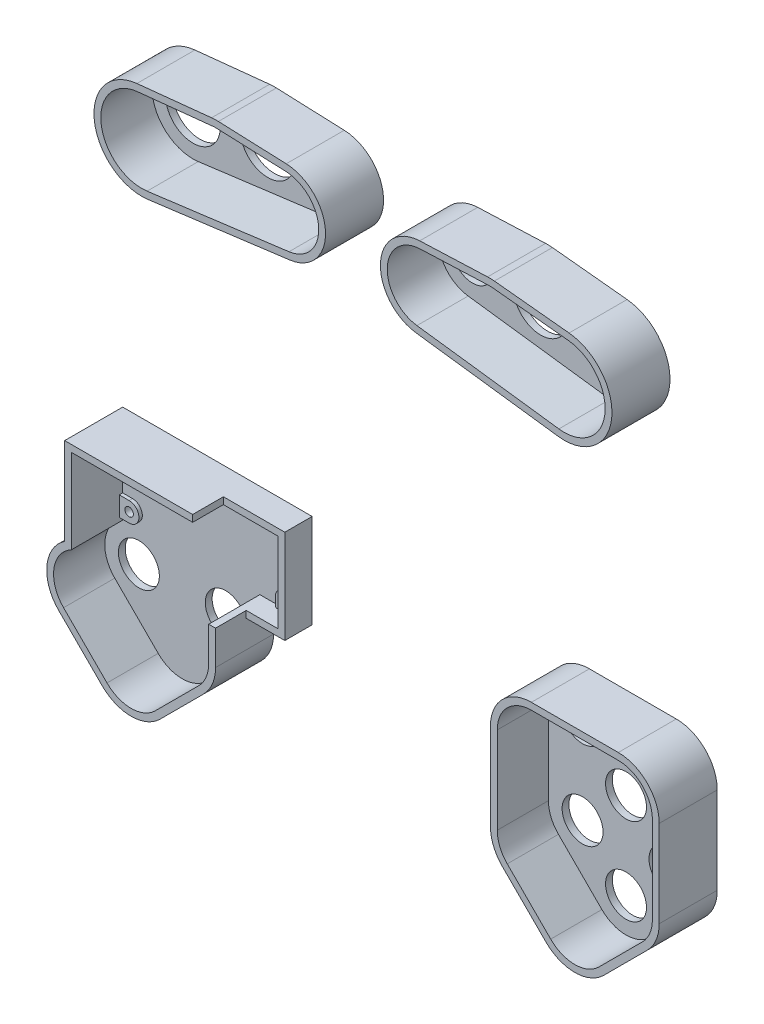
SolidWorks part; units mm, degrees
ref_plane "Front Plane" through (0, 0, 0) normal (0, 0, 1) x (1, 0, 0)
ref_plane "Top Plane" through (0, 0, 0) normal (0, 1, 0) x (1, 0, 0)
ref_plane "Right Plane" through (0, 0, 0) normal (1, 0, 0) x (0, 0, -1)
sketch "Sketch1" plane through (0, 0, 0) normal (0, 0, 1) x (1, 0, 0)
  line L10 (-86.2132, -68.4853) -> (-73.4853, -81.2132)
  line L11 (-56.5147, -81.2132) -> (-43.7868, -68.4853)
  line L12 (43.7868, -68.4853) -> (56.5147, -81.2132)
  line L13 (73.4853, -81.2132) -> (86.2132, -68.4853)
  line L14 (89.7279, -60) -> (89.7279, -34.5442)
  line L15 (63.3122, 76.6851) -> (41.4267, 78.9271)
  line L16 (39.439, 78.9888) -> (19.5552, 78.1913)
  line L17 (-19.5552, 78.1913) -> (-39.439, 78.9888)
  line L18 (-41.4267, 78.9271) -> (-63.3122, 76.6851)
  line L19 (-89.7279, -34.5442) -> (-89.7279, -60)
  line L20 (-86.2132, -68.4853) -> (-73.4853, -81.2132)
  line L21 (-56.5147, -81.2132) -> (-43.7868, -68.4853)
  line L22 (43.7868, -68.4853) -> (56.5147, -81.2132)
  line L23 (73.4853, -81.2132) -> (86.2132, -68.4853)
  line L24 (89.7279, -60) -> (89.7279, -34.5442)
  line L25 (63.3122, 76.6851) -> (41.4267, 78.9271)
  line L26 (39.439, 78.9888) -> (19.5552, 78.1913)
  line L27 (-19.5552, 78.1913) -> (-39.439, 78.9888)
  line L28 (-41.4267, 78.9271) -> (-63.3122, 76.6851)
  line L29 (-89.7279, -34.5442) -> (-89.7279, -60)
  line L30 (77.7279, -22.5442) -> (52.2721, -22.5442)
  line L31 (40.2721, -34.5442) -> (40.2721, -60)
  line L32 (-60.0743, 48.8756) -> (-18.4837, 54.3018)
  line L33 (60.0743, 48.8756) -> (18.4837, 54.3018)
  line L34 (-77.7279, -48) -> (-52.2721, -48)
  line L35 (-65, -48) -> (-65, -50) construction
  line L36 (-79.579, -29.36) -> (-33.859, -29.36)
  line L37 (-79.579, -29.36) -> (-79.579, -47.14)
  line L38 (-79.579, -47.14) -> (-33.859, -47.14)
  line L39 (-33.859, -29.36) -> (-33.859, -47.14)
  line L40 (-79.579, -29.36) -> (-33.859, -47.14) construction
  line L41 (-79.579, -47.14) -> (-33.859, -29.36) construction
  line L42 (-82.469, -26.5) -> (-30.969, -26.5)
  line L43 (-82.469, -26.5) -> (-82.469, -50)
  line L44 (-82.469, -50) -> (-30.969, -50)
  line L45 (-30.969, -26.5) -> (-30.969, -50)
  line L46 (-82.469, -26.5) -> (-30.969, -50) construction
  line L47 (-82.469, -50) -> (-30.969, -26.5) construction
  line L48 (-84.469, -52) -> (-28.969, -52)
  line L49 (-84.469, -52) -> (-84.469, -24.5)
  line L50 (-84.469, -24.5) -> (-28.969, -24.5)
  line L51 (-28.969, -52) -> (-28.969, -24.5)
  line L52 (-84.469, -52) -> (-28.969, -24.5) construction
  line L53 (-84.469, -24.5) -> (-28.969, -52) construction
  line L54 (-30.969, -26.5) -> (-28.969, -26.5) construction
  line L55 (-30.969, -26.5) -> (-30.969, -24.5) construction
  line L56 (-40.2721, -60) -> (-40.2721, -52)
  arc A16 (-89.7279, -60) -> (-86.2132, -68.4853) centre (-77.7279, -60) ccw
  arc A17 (-73.4853, -81.2132) -> (-56.5147, -81.2132) centre (-65, -72.7279) ccw
  arc A18 (43.7868, -68.4853) -> (-43.7868, -68.4853) centre (0, -112.2721) ccw
  arc A19 (56.5147, -81.2132) -> (73.4853, -81.2132) centre (65, -72.7279) ccw
  arc A20 (86.2132, -68.4853) -> (89.7279, -60) centre (77.7279, -60) ccw
  arc A21 (89.7279, -34.5442) -> (85.5204, -25.4185) centre (77.7279, -34.5442) ccw
  arc A22 (73.6585, 55.182) -> (85.5204, -25.4185) centre (125.7323, 21.6725) ccw
  arc A23 (73.6585, 55.182) -> (63.3122, 76.6851) centre (61.8855, 62.758) ccw
  arc A24 (41.4267, 78.9271) -> (39.439, 78.9888) centre (40, 65) ccw
  arc A25 (19.5552, 78.1913) -> (16.7836, 77.7518) centre (20.0361, 66.201) ccw
  arc A26 (-16.7836, 77.7518) -> (16.7836, 77.7518) centre (0, 137.3578) ccw
  arc A27 (-16.7836, 77.7518) -> (-19.5552, 78.1913) centre (-20.0361, 66.201) ccw
  arc A28 (-39.439, 78.9888) -> (-41.4267, 78.9271) centre (-40, 65) ccw
  arc A29 (-63.3122, 76.6851) -> (-73.6585, 55.182) centre (-61.8855, 62.758) ccw
  arc A30 (-85.5204, -25.4185) -> (-73.6585, 55.182) centre (-125.7323, 21.6725) ccw
  arc A31 (-85.5204, -25.4185) -> (-89.7279, -34.5442) centre (-77.7279, -34.5442) ccw
  arc A32 (-89.7279, -60) -> (-86.2132, -68.4853) centre (-77.7279, -60) ccw
  arc A33 (-73.4853, -81.2132) -> (-56.5147, -81.2132) centre (-65, -72.7279) ccw
  arc A34 (43.7868, -68.4853) -> (-43.7868, -68.4853) centre (0, -112.2721) ccw
  arc A35 (56.5147, -81.2132) -> (73.4853, -81.2132) centre (65, -72.7279) ccw
  arc A36 (86.2132, -68.4853) -> (89.7279, -60) centre (77.7279, -60) ccw
  arc A37 (89.7279, -34.5442) -> (85.5204, -25.4185) centre (77.7279, -34.5442) ccw
  arc A38 (73.6585, 55.182) -> (85.5204, -25.4185) centre (125.7323, 21.6725) ccw
  arc A39 (73.6585, 55.182) -> (63.3122, 76.6851) centre (61.8855, 62.758) ccw
  arc A40 (41.4267, 78.9271) -> (39.439, 78.9888) centre (40, 65) ccw
  arc A41 (19.5552, 78.1913) -> (16.7836, 77.7518) centre (20.0361, 66.201) ccw
  arc A42 (-16.7836, 77.7518) -> (16.7836, 77.7518) centre (0, 137.3578) ccw
  arc A43 (-16.7836, 77.7518) -> (-19.5552, 78.1913) centre (-20.0361, 66.201) ccw
  arc A44 (-39.439, 78.9888) -> (-41.4267, 78.9271) centre (-40, 65) ccw
  arc A45 (-63.3122, 76.6851) -> (-73.6585, 55.182) centre (-61.8855, 62.758) ccw
  arc A46 (-85.5204, -25.4185) -> (-73.6585, 55.182) centre (-125.7323, 21.6725) ccw
  arc A47 (-85.5204, -25.4185) -> (-89.7279, -34.5442) centre (-77.7279, -34.5442) ccw
  circle A48 centre (77.7279, -34.5442) radius 6 construction
  circle A49 centre (52.2721, -34.5442) radius 6 construction
  circle A50 centre (65, -47.2721) radius 6 construction
  circle A51 centre (77.7279, -60) radius 6 construction
  circle A52 centre (52.2721, -60) radius 6 construction
  circle A53 centre (65, -72.7279) radius 6 construction
  circle A54 centre (-52.2721, -60) radius 6 construction
  circle A55 centre (-77.7279, -60) radius 6 construction
  circle A56 centre (77.7279, -34.5442) radius 6
  circle A57 centre (52.2721, -34.5442) radius 6
  circle A58 centre (65, -47.2721) radius 6
  circle A59 centre (77.7279, -60) radius 6
  circle A60 centre (52.2721, -60) radius 6
  circle A61 centre (65, -72.7279) radius 6
  circle A62 centre (-52.2721, -60) radius 6
  circle A63 centre (-77.7279, -60) radius 6
  circle A64 centre (61.8855, 62.758) radius 8 construction
  circle A65 centre (40, 65) radius 8 construction
  circle A66 centre (20.0361, 66.201) radius 6 construction
  circle A67 centre (-20.0361, 66.201) radius 6 construction
  circle A68 centre (-40, 65) radius 8 construction
  circle A69 centre (-61.8855, 62.758) radius 8 construction
  circle A70 centre (61.8855, 62.758) radius 8
  circle A71 centre (40, 65) radius 8
  circle A72 centre (20.0361, 66.201) radius 6
  circle A73 centre (-20.0361, 66.201) radius 6
  circle A74 centre (-40, 65) radius 8
  circle A75 centre (-61.8855, 62.758) radius 8
  circle A76 centre (77.7279, -34.5442) radius 12
  circle A77 centre (52.2721, -34.5442) radius 12
  circle A78 centre (52.2721, -60) radius 12
  circle A79 centre (-61.8855, 62.758) radius 14
  circle A80 centre (-20.0361, 66.201) radius 12
  circle A81 centre (20.0361, 66.201) radius 12
  circle A82 centre (61.8855, 62.758) radius 14
  circle A83 centre (-77.7279, -60) radius 12
  circle A84 centre (-52.2721, -60) radius 12
  circle A85 centre (-79.579, -29.36) radius 1.25
  circle A86 centre (-33.859, -29.36) radius 1.25
  circle A87 centre (-33.859, -47.14) radius 1.25
  circle A88 centre (-79.579, -47.14) radius 1.25
  point P47 (-56.719, -38.25)
  point P66 (-56.719, -38.25)
  point P72 (-56.719, -38.25)
  dimension "D4" = 2.5
  dimension "D2" = 45.72
  dimension "D3" = 17.78
  dimension "D5" = 51.5
  dimension "D6" = 23.5
  dimension "D7" = 2
  dimension "D1" = 0
extrude "Boss-Extrude1" add sketch "Sketch1" along normal blind 2 contours A84 L34 A83 L20 A33 L21 | A83 A32 A63 | A84 A62 | A37 A76 A56 | A77 A58 A76 L30 | A77 A57 | A78 A58 A77 L31 | A78 L22 A35 L23 A36 L24 A76 A58 A61 A59 | A78 A60 | A79 A45 A75 | A80 A74 A79 L32 | A80 L27 A44 L28 A79 A74 | A43 A80 A73 | A41 A81 A72 | A82 L25 A40 L26 A81 A71 | A82 A71 A81 L33 | A39 A82 A70 | A84 L56 L48 | A84 L48 L51 L50 L49 A83 L43 L42 L45 L44 | L48 A84 L44 | A84 L44 A83 L48 | L48 A83 L44 L43 L49 | A88 A83 L43 L44 | A84 L34 A83 L44 | L44 A84 | A88 L37 A85 L36 A86 L39 A87 L38 A83 L34 A84 L44 L45 L42 L43 | A88 L38 A87 L39 A86 L36 A85 L37 region at (-65, -73.7209, 0) region at (-88.5141, -64.4678, 0) region at (-77.3432, -50.979, 0) region at (-83.8496, -37.2862, 0) region at (-65, -50.921, 0) region at (-60.3032, -68.4912, 0) region at (-77.3671, -49.1806, 0) region at (-81.9029, -37.7381, 0) region at (-52.2721, -51.0485, 0) region at (-65, -48.8938, 0) region at (52.2721, -72.6804, 0) region at (41.4991, -64.4623, 0) region at (-41.1646, -53.9455, 0) region at (-74.1443, 68.6564, 0) region at (-52.2721, -49.194, 0) region at (46.3766, -47.2721, 0) region at (-41.0869, 74.8949, 0) region at (-39.4755, 55.0305, 0) region at (-56.719, -38.25, 0) region at (44.0268, -26.2989, 0) region at (-27.4629, 57.2114, 0) region at (65, -28.6487, 0) region at (81.7633, -23.6041, 0) region at (18.2097, 77.7176, 0) region at (67.6138, 50.4188, 0) region at (41.0869, 74.8949, 0) region at (39.4755, 55.0305, 0)
sketch "Sketch2" plane through (0, 0, 2) normal (0, 0, 1) x (1, 0, 0)
  line L0 (40.2721, -34.5442) -> (40.2721, -60) construction
  line L1 (43.7868, -68.4853) -> (56.5147, -81.2132) construction
  line L2 (73.4853, -81.2132) -> (86.2132, -68.4853) construction
  line L3 (89.7279, -60) -> (89.7279, -34.5442) construction
  line L4 (77.7279, -22.5442) -> (52.2721, -22.5442) construction
  line L5 (18.4837, 54.3018) -> (60.0743, 48.8756) construction
  line L6 (63.3122, 76.6851) -> (41.4267, 78.9271) construction
  line L7 (39.439, 78.9888) -> (19.5552, 78.1913) construction
  line L8 (-19.5552, 78.1913) -> (-39.439, 78.9888) construction
  line L9 (-41.4267, 78.9271) -> (-63.3122, 76.6851) construction
  line L10 (-60.0743, 48.8756) -> (-18.4837, 54.3018) construction
  line L14 (40.2721, -34.5442) -> (40.2721, -60)
  line L15 (43.7868, -68.4853) -> (56.5147, -81.2132)
  line L16 (73.4853, -81.2132) -> (86.2132, -68.4853)
  line L17 (89.7279, -60) -> (89.7279, -34.5442)
  line L18 (77.7279, -22.5442) -> (52.2721, -22.5442)
  line L19 (18.4837, 54.3018) -> (60.0743, 48.8756)
  line L20 (63.3122, 76.6851) -> (41.4267, 78.9271)
  line L21 (39.439, 78.9888) -> (19.5552, 78.1913)
  line L22 (-19.5552, 78.1913) -> (-39.439, 78.9888)
  line L23 (-41.4267, 78.9271) -> (-63.3122, 76.6851)
  line L24 (-60.0743, 48.8756) -> (-18.4837, 54.3018)
  line L31 (-19.6354, 76.1929) -> (-39.5191, 76.9904)
  line L32 (-41.2229, 76.9375) -> (-63.1084, 74.6955)
  line L33 (-60.333, 50.8588) -> (-18.7424, 56.285)
  line L34 (18.7424, 56.285) -> (60.333, 50.8588)
  line L35 (63.1084, 74.6955) -> (41.2229, 76.9375)
  line L36 (39.5191, 76.9904) -> (19.6354, 76.1929)
  line L37 (42.2721, -34.5442) -> (42.2721, -60)
  line L38 (45.201, -67.0711) -> (57.9289, -79.799)
  line L39 (72.0711, -79.799) -> (84.799, -67.0711)
  line L40 (87.7279, -60) -> (87.7279, -34.5442)
  line L41 (77.7279, -24.5442) -> (52.2721, -24.5442)
  line L49 (-40.2721, -60) -> (-40.2721, -52)
  line L50 (-40.2721, -52) -> (-28.969, -52)
  line L51 (-28.969, -52) -> (-28.969, -24.5)
  line L52 (-28.969, -24.5) -> (-84.469, -24.5)
  line L53 (-84.469, -24.5) -> (-84.469, -50.0724)
  line L54 (-86.2132, -68.4853) -> (-73.4853, -81.2132)
  line L55 (-56.5147, -81.2132) -> (-43.7868, -68.4853)
  line L56 (-40.2721, -60) -> (-40.2721, -52)
  line L57 (-40.2721, -52) -> (-28.969, -52)
  line L58 (-28.969, -52) -> (-28.969, -24.5)
  line L59 (-28.969, -24.5) -> (-84.469, -24.5)
  line L60 (-84.469, -24.5) -> (-84.469, -50.0724)
  line L61 (-86.2132, -68.4853) -> (-73.4853, -81.2132)
  line L62 (-56.5147, -81.2132) -> (-43.7868, -68.4853)
  line L70 (-42.2721, -60) -> (-42.2721, -50)
  line L71 (-42.2721, -50) -> (-30.969, -50)
  line L72 (-30.969, -50) -> (-30.969, -26.5)
  line L73 (-30.969, -26.5) -> (-82.469, -26.5)
  line L74 (-82.469, -26.5) -> (-82.469, -51.1953)
  line L75 (-84.799, -67.0711) -> (-72.0711, -79.799)
  line L76 (-57.9289, -79.799) -> (-45.201, -67.0711)
  line L77 (-42.2721, -60) -> (-42.2721, -50)
  line L78 (-42.2721, -50) -> (-30.969, -50)
  line L79 (-30.969, -50) -> (-30.969, -26.5)
  line L80 (-30.969, -26.5) -> (-82.469, -26.5)
  line L81 (-82.469, -26.5) -> (-82.469, -51.1953)
  line L82 (-84.799, -67.0711) -> (-72.0711, -79.799)
  line L83 (-57.9289, -79.799) -> (-45.201, -67.0711)
  arc A0 (40.2721, -60) -> (43.7868, -68.4853) centre (52.2721, -60) ccw construction
  arc A1 (56.5147, -81.2132) -> (73.4853, -81.2132) centre (65, -72.7279) ccw construction
  arc A2 (86.2132, -68.4853) -> (89.7279, -60) centre (77.7279, -60) ccw construction
  arc A3 (89.7279, -34.5442) -> (77.7279, -22.5442) centre (77.7279, -34.5442) ccw construction
  arc A4 (52.2721, -22.5442) -> (40.2721, -34.5442) centre (52.2721, -34.5442) ccw construction
  arc A5 (60.0743, 48.8756) -> (63.3122, 76.6851) centre (61.8855, 62.758) ccw construction
  arc A6 (41.4267, 78.9271) -> (39.439, 78.9888) centre (40, 65) ccw construction
  arc A7 (19.5552, 78.1913) -> (18.4837, 54.3018) centre (20.0361, 66.201) ccw construction
  arc A8 (-18.4837, 54.3018) -> (-19.5552, 78.1913) centre (-20.0361, 66.201) ccw construction
  arc A9 (-39.439, 78.9888) -> (-41.4267, 78.9271) centre (-40, 65) ccw construction
  arc A10 (-63.3122, 76.6851) -> (-60.0743, 48.8756) centre (-61.8855, 62.758) ccw construction
  arc A14 (40.2721, -60) -> (43.7868, -68.4853) centre (52.2721, -60) ccw
  arc A15 (56.5147, -81.2132) -> (73.4853, -81.2132) centre (65, -72.7279) ccw
  arc A16 (86.2132, -68.4853) -> (89.7279, -60) centre (77.7279, -60) ccw
  arc A17 (89.7279, -34.5442) -> (77.7279, -22.5442) centre (77.7279, -34.5442) ccw
  arc A18 (52.2721, -22.5442) -> (40.2721, -34.5442) centre (52.2721, -34.5442) ccw
  arc A19 (60.0743, 48.8756) -> (63.3122, 76.6851) centre (61.8855, 62.758) ccw
  arc A20 (41.4267, 78.9271) -> (39.439, 78.9888) centre (40, 65) ccw
  arc A21 (19.5552, 78.1913) -> (18.4837, 54.3018) centre (20.0361, 66.201) ccw
  arc A22 (-18.4837, 54.3018) -> (-19.5552, 78.1913) centre (-20.0361, 66.201) ccw
  arc A23 (-39.439, 78.9888) -> (-41.4267, 78.9271) centre (-40, 65) ccw
  arc A24 (-63.3122, 76.6851) -> (-60.0743, 48.8756) centre (-61.8855, 62.758) ccw
  arc A31 (-18.7424, 56.285) -> (-19.6354, 76.1929) centre (-20.0361, 66.201) ccw
  arc A32 (-39.5191, 76.9904) -> (-41.2229, 76.9375) centre (-40, 65) ccw
  arc A33 (-63.1084, 74.6955) -> (-60.333, 50.8588) centre (-61.8855, 62.758) ccw
  arc A34 (60.333, 50.8588) -> (63.1084, 74.6955) centre (61.8855, 62.758) ccw
  arc A35 (41.2229, 76.9375) -> (39.5191, 76.9904) centre (40, 65) ccw
  arc A36 (19.6354, 76.1929) -> (18.7424, 56.285) centre (20.0361, 66.201) ccw
  arc A37 (42.2721, -60) -> (45.201, -67.0711) centre (52.2721, -60) ccw
  arc A38 (57.9289, -79.799) -> (72.0711, -79.799) centre (65, -72.7279) ccw
  arc A39 (84.799, -67.0711) -> (87.7279, -60) centre (77.7279, -60) ccw
  arc A40 (87.7279, -34.5442) -> (77.7279, -24.5442) centre (77.7279, -34.5442) ccw
  arc A41 (52.2721, -24.5442) -> (42.2721, -34.5442) centre (52.2721, -34.5442) ccw
  arc A45 (-84.469, -50.0724) -> (-86.2132, -68.4853) centre (-77.7279, -60) ccw
  arc A46 (-73.4853, -81.2132) -> (-56.5147, -81.2132) centre (-65, -72.7279) ccw
  arc A47 (-43.7868, -68.4853) -> (-40.2721, -60) centre (-52.2721, -60) ccw
  arc A48 (-84.469, -50.0724) -> (-86.2132, -68.4853) centre (-77.7279, -60) ccw
  arc A49 (-73.4853, -81.2132) -> (-56.5147, -81.2132) centre (-65, -72.7279) ccw
  arc A50 (-43.7868, -68.4853) -> (-40.2721, -60) centre (-52.2721, -60) ccw
  arc A54 (-82.469, -51.1953) -> (-84.799, -67.0711) centre (-77.7279, -60) ccw
  arc A55 (-72.0711, -79.799) -> (-57.9289, -79.799) centre (-65, -72.7279) ccw
  arc A56 (-45.201, -67.0711) -> (-42.2721, -60) centre (-52.2721, -60) ccw
  arc A57 (-82.469, -51.1953) -> (-84.799, -67.0711) centre (-77.7279, -60) ccw
  arc A58 (-72.0711, -79.799) -> (-57.9289, -79.799) centre (-65, -72.7279) ccw
  arc A59 (-45.201, -67.0711) -> (-42.2721, -60) centre (-52.2721, -60) ccw
  dimension "D1" = 2
  dimension "D2" = 0
  dimension "D3" = 2
extrude "Boss-Extrude2" add sketch "Sketch2" along normal blind 6
sketch "Sketch3" plane through (0, 0, 2) normal (0, 0, 1) x (1, 0, 0)
  line L0 (-30.969, -26.5) -> (-82.469, -26.5) construction
  line L1 (-76.719, -29.36) -> (-76.719, -26.5)
  line L2 (-79.579, -32.22) -> (-82.469, -32.22)
  line L3 (-82.469, -26.5) -> (-82.469, -51.1953) construction
  line L4 (-79.579, -44.28) -> (-82.469, -44.28)
  line L5 (-82.469, -26.5) -> (-82.469, -51.1953) construction
  line L6 (-79.579, -50) -> (-82.469, -50)
  line L7 (-36.719, -29.36) -> (-36.719, -26.5)
  line L8 (-30.969, -26.5) -> (-82.469, -26.5) construction
  line L9 (-33.859, -32.22) -> (-30.969, -32.22)
  line L10 (-30.969, -50) -> (-30.969, -26.5) construction
  line L11 (-33.859, -44.28) -> (-30.969, -44.28)
  line L12 (-36.719, -47.14) -> (-36.6205, -50)
  line L13 (-42.2721, -50) -> (-30.969, -50) construction
  line L21 (-57.9289, -79.799) -> (-45.201, -67.0711)
  line L22 (-42.2721, -60) -> (-42.2721, -50)
  line L23 (-42.2721, -50) -> (-30.969, -50)
  line L24 (-30.969, -50) -> (-30.969, -26.5)
  line L25 (-30.969, -26.5) -> (-82.469, -26.5)
  line L26 (-82.469, -26.5) -> (-82.469, -51.1953)
  line L27 (-84.799, -67.0711) -> (-72.0711, -79.799)
  line L28 (-57.9289, -79.799) -> (-45.201, -67.0711)
  line L29 (-42.2721, -60) -> (-42.2721, -50)
  line L30 (-42.2721, -50) -> (-30.969, -50)
  line L31 (-30.969, -50) -> (-30.969, -26.5)
  line L32 (-30.969, -26.5) -> (-82.469, -26.5)
  line L33 (-82.469, -26.5) -> (-82.469, -51.1953)
  line L34 (-84.799, -67.0711) -> (-72.0711, -79.799)
  circle A0 centre (-33.859, -47.14) radius 1.25 construction
  circle A1 centre (-33.859, -29.36) radius 1.25 construction
  circle A2 centre (-79.579, -47.14) radius 1.25 construction
  circle A3 centre (-79.579, -29.36) radius 1.25 construction
  circle A4 centre (-33.859, -47.14) radius 1.25
  circle A5 centre (-33.859, -29.36) radius 1.25
  circle A6 centre (-79.579, -47.14) radius 1.25
  circle A7 centre (-79.579, -29.36) radius 1.25
  circle A8 centre (-79.579, -29.36) radius 2.86
  circle A9 centre (-33.859, -29.36) radius 2.86
  circle A10 centre (-33.859, -47.14) radius 2.86
  circle A11 centre (-79.579, -47.14) radius 2.86
  arc A15 (-45.201, -67.0711) -> (-42.2721, -60) centre (-52.2721, -60) ccw
  arc A16 (-82.469, -51.1953) -> (-84.799, -67.0711) centre (-77.7279, -60) ccw
  arc A17 (-72.0711, -79.799) -> (-57.9289, -79.799) centre (-65, -72.7279) ccw
  arc A18 (-45.201, -67.0711) -> (-42.2721, -60) centre (-52.2721, -60) ccw
  arc A19 (-82.469, -51.1953) -> (-84.799, -67.0711) centre (-77.7279, -60) ccw
  arc A20 (-72.0711, -79.799) -> (-57.9289, -79.799) centre (-65, -72.7279) ccw
  circle M20 centre (-79.579, -29.36) radius 1.25
  circle M21 centre (-33.859, -47.14) radius 1.25
  circle M22 centre (-33.859, -29.36) radius 1.25
  circle M23 centre (-79.579, -47.14) radius 1.25
  line M27 (-42.2721, -50) -> (-30.969, -50)
  line M28 (-30.969, -50) -> (-30.969, -26.5)
  line M29 (-30.969, -26.5) -> (-82.469, -26.5)
  line M30 (-82.469, -26.5) -> (-82.469, -51.1953)
  dimension "D1" = 0
extrude "Boss-Extrude3" add sketch "Sketch3" along normal blind 1 contours A8 M20 | A8 L1 M29 | A8 L32 L2 M30 | A9 L32 L7 | A9 M22 | A9 L9 M28 M29 | A10 L30 L11 M28 | A10 L12 M21 | A10 L12 M27 | A11 L4 L6 M30 | A11 M23 region at (-77.3578, -27.1388, 2) region at (-77.6139, -31.3251, 2) region at (-81.024, -32.1559, 2) region at (-36.0802, -27.1388, 2) region at (-35.8241, -27.3949, 2) region at (-32.414, -26.5641, 2) region at (-81.024, -44.3441, 2) region at (-77.6139, -45.1749, 2) region at (-30.9754, -47.14, 2) region at (-31.8939, -45.1749, 2) region at (-36.0274, -49.3883, 2)
sketch "Sketch4" plane through (0, 0, 8) normal (0, 0, 1) x (1, 0, 0)
  line L0 (-40.2721, -52) -> (-40.2721, -50)
  line L1 (-46.969, -26.5) -> (-46.969, -24.5)
  line L4 (-19.5552, 78.1913) -> (-39.439, 78.9888)
  line L5 (-41.4267, 78.9271) -> (-63.3122, 76.6851)
  line L6 (-60.0743, 48.8756) -> (-18.4837, 54.3018)
  line L7 (-40.2721, -60) -> (-40.2721, -52)
  line L8 (-40.2721, -52) -> (-28.969, -52)
  line L9 (-28.969, -52) -> (-28.969, -24.5)
  line L10 (-28.969, -24.5) -> (-84.469, -24.5)
  line L11 (-84.469, -24.5) -> (-84.469, -50.0724)
  line L12 (-86.2132, -68.4853) -> (-73.4853, -81.2132)
  line L13 (-56.5147, -81.2132) -> (-43.7868, -68.4853)
  line L14 (-40.2721, -60) -> (-40.2721, -52)
  line L15 (-40.2721, -52) -> (-28.969, -52)
  line L16 (-28.969, -52) -> (-28.969, -24.5)
  line L17 (-28.969, -24.5) -> (-84.469, -24.5)
  line L18 (-84.469, -24.5) -> (-84.469, -50.0724)
  line L19 (-86.2132, -68.4853) -> (-73.4853, -81.2132)
  line L20 (-56.5147, -81.2132) -> (-43.7868, -68.4853)
  line L21 (-19.5552, 78.1913) -> (-39.439, 78.9888)
  line L22 (-42.2721, -60) -> (-42.2721, -50)
  line L23 (-57.9289, -79.799) -> (-45.201, -67.0711)
  line L24 (-84.799, -67.0711) -> (-72.0711, -79.799)
  line L25 (-82.469, -26.5) -> (-82.469, -51.1953)
  line L26 (-30.969, -26.5) -> (-82.469, -26.5)
  line L27 (-30.969, -50) -> (-30.969, -26.5)
  line L28 (-42.2721, -50) -> (-30.969, -50)
  line L29 (-42.2721, -60) -> (-42.2721, -50)
  line L30 (-57.9289, -79.799) -> (-45.201, -67.0711)
  line L31 (-84.799, -67.0711) -> (-72.0711, -79.799)
  line L32 (-82.469, -26.5) -> (-82.469, -51.1953)
  line L33 (-30.969, -26.5) -> (-82.469, -26.5)
  line L34 (-30.969, -50) -> (-30.969, -26.5)
  line L35 (-42.2721, -50) -> (-30.969, -50)
  line L36 (-41.4267, 78.9271) -> (-63.3122, 76.6851)
  line L37 (-60.0743, 48.8756) -> (-18.4837, 54.3018)
  line L38 (-19.6354, 76.1929) -> (-39.5191, 76.9904)
  line L39 (-60.333, 50.8588) -> (-18.7424, 56.285)
  line L40 (-41.2229, 76.9375) -> (-63.1084, 74.6955)
  line L41 (-19.6354, 76.1929) -> (-39.5191, 76.9904)
  line L42 (-60.333, 50.8588) -> (-18.7424, 56.285)
  line L43 (-41.2229, 76.9375) -> (-63.1084, 74.6955)
  line L44 (18.4837, 54.3018) -> (60.0743, 48.8756)
  line L45 (63.3122, 76.6851) -> (41.4267, 78.9271)
  line L46 (39.439, 78.9888) -> (19.5552, 78.1913)
  line L47 (18.4837, 54.3018) -> (60.0743, 48.8756)
  line L48 (63.3122, 76.6851) -> (41.4267, 78.9271)
  line L49 (39.439, 78.9888) -> (19.5552, 78.1913)
  line L50 (18.7424, 56.285) -> (60.333, 50.8588)
  line L51 (39.5191, 76.9904) -> (19.6354, 76.1929)
  line L52 (63.1084, 74.6955) -> (41.2229, 76.9375)
  line L53 (18.7424, 56.285) -> (60.333, 50.8588)
  line L54 (39.5191, 76.9904) -> (19.6354, 76.1929)
  line L55 (63.1084, 74.6955) -> (41.2229, 76.9375)
  line L58 (40.2721, -34.5442) -> (40.2721, -60)
  line L59 (43.7868, -68.4853) -> (56.5147, -81.2132)
  line L60 (73.4853, -81.2132) -> (86.2132, -68.4853)
  line L61 (89.7279, -60) -> (89.7279, -34.5442)
  line L62 (77.7279, -22.5442) -> (52.2721, -22.5442)
  line L63 (40.2721, -34.5442) -> (40.2721, -60)
  line L64 (43.7868, -68.4853) -> (56.5147, -81.2132)
  line L65 (73.4853, -81.2132) -> (86.2132, -68.4853)
  line L66 (89.7279, -60) -> (89.7279, -34.5442)
  line L67 (77.7279, -22.5442) -> (52.2721, -22.5442)
  line L69 (42.2721, -34.5442) -> (42.2721, -60)
  line L70 (77.7279, -24.5442) -> (52.2721, -24.5442)
  line L71 (87.7279, -60) -> (87.7279, -34.5442)
  line L72 (72.0711, -79.799) -> (84.799, -67.0711)
  line L73 (45.201, -67.0711) -> (57.9289, -79.799)
  line L74 (42.2721, -34.5442) -> (42.2721, -60)
  line L75 (77.7279, -24.5442) -> (52.2721, -24.5442)
  line L76 (87.7279, -60) -> (87.7279, -34.5442)
  line L77 (72.0711, -79.799) -> (84.799, -67.0711)
  line L78 (45.201, -67.0711) -> (57.9289, -79.799)
  arc A3 (-43.7868, -68.4853) -> (-40.2721, -60) centre (-52.2721, -60) ccw
  arc A4 (-84.469, -50.0724) -> (-86.2132, -68.4853) centre (-77.7279, -60) ccw
  arc A5 (-73.4853, -81.2132) -> (-56.5147, -81.2132) centre (-65, -72.7279) ccw
  arc A6 (-43.7868, -68.4853) -> (-40.2721, -60) centre (-52.2721, -60) ccw
  arc A7 (-84.469, -50.0724) -> (-86.2132, -68.4853) centre (-77.7279, -60) ccw
  arc A8 (-73.4853, -81.2132) -> (-56.5147, -81.2132) centre (-65, -72.7279) ccw
  arc A9 (-45.201, -67.0711) -> (-42.2721, -60) centre (-52.2721, -60) ccw
  arc A10 (-72.0711, -79.799) -> (-57.9289, -79.799) centre (-65, -72.7279) ccw
  arc A11 (-82.469, -51.1953) -> (-84.799, -67.0711) centre (-77.7279, -60) ccw
  arc A12 (-45.201, -67.0711) -> (-42.2721, -60) centre (-52.2721, -60) ccw
  arc A13 (-72.0711, -79.799) -> (-57.9289, -79.799) centre (-65, -72.7279) ccw
  arc A14 (-82.469, -51.1953) -> (-84.799, -67.0711) centre (-77.7279, -60) ccw
  arc A15 (-18.4837, 54.3018) -> (-19.5552, 78.1913) centre (-20.0361, 66.201) ccw
  arc A16 (-39.439, 78.9888) -> (-41.4267, 78.9271) centre (-40, 65) ccw
  arc A17 (-63.3122, 76.6851) -> (-60.0743, 48.8756) centre (-61.8855, 62.758) ccw
  arc A18 (-18.4837, 54.3018) -> (-19.5552, 78.1913) centre (-20.0361, 66.201) ccw
  arc A19 (-39.439, 78.9888) -> (-41.4267, 78.9271) centre (-40, 65) ccw
  arc A20 (-63.3122, 76.6851) -> (-60.0743, 48.8756) centre (-61.8855, 62.758) ccw
  arc A22 (-18.7424, 56.285) -> (-19.6354, 76.1929) centre (-20.0361, 66.201) ccw
  arc A23 (-63.1084, 74.6955) -> (-60.333, 50.8588) centre (-61.8855, 62.758) ccw
  arc A24 (-39.5191, 76.9904) -> (-41.2229, 76.9375) centre (-40, 65) ccw
  arc A25 (-18.7424, 56.285) -> (-19.6354, 76.1929) centre (-20.0361, 66.201) ccw
  arc A26 (-63.1084, 74.6955) -> (-60.333, 50.8588) centre (-61.8855, 62.758) ccw
  arc A27 (-39.5191, 76.9904) -> (-41.2229, 76.9375) centre (-40, 65) ccw
  arc A28 (19.5552, 78.1913) -> (18.4837, 54.3018) centre (20.0361, 66.201) ccw
  arc A29 (60.0743, 48.8756) -> (63.3122, 76.6851) centre (61.8855, 62.758) ccw
  arc A30 (41.4267, 78.9271) -> (39.439, 78.9888) centre (40, 65) ccw
  arc A31 (19.5552, 78.1913) -> (18.4837, 54.3018) centre (20.0361, 66.201) ccw
  arc A32 (60.0743, 48.8756) -> (63.3122, 76.6851) centre (61.8855, 62.758) ccw
  arc A33 (41.4267, 78.9271) -> (39.439, 78.9888) centre (40, 65) ccw
  arc A35 (19.6354, 76.1929) -> (18.7424, 56.285) centre (20.0361, 66.201) ccw
  arc A36 (41.2229, 76.9375) -> (39.5191, 76.9904) centre (40, 65) ccw
  arc A37 (60.333, 50.8588) -> (63.1084, 74.6955) centre (61.8855, 62.758) ccw
  arc A38 (19.6354, 76.1929) -> (18.7424, 56.285) centre (20.0361, 66.201) ccw
  arc A39 (41.2229, 76.9375) -> (39.5191, 76.9904) centre (40, 65) ccw
  arc A40 (60.333, 50.8588) -> (63.1084, 74.6955) centre (61.8855, 62.758) ccw
  arc A43 (52.2721, -22.5442) -> (40.2721, -34.5442) centre (52.2721, -34.5442) ccw
  arc A44 (40.2721, -60) -> (43.7868, -68.4853) centre (52.2721, -60) ccw
  arc A45 (56.5147, -81.2132) -> (73.4853, -81.2132) centre (65, -72.7279) ccw
  arc A46 (86.2132, -68.4853) -> (89.7279, -60) centre (77.7279, -60) ccw
  arc A47 (89.7279, -34.5442) -> (77.7279, -22.5442) centre (77.7279, -34.5442) ccw
  arc A48 (52.2721, -22.5442) -> (40.2721, -34.5442) centre (52.2721, -34.5442) ccw
  arc A49 (40.2721, -60) -> (43.7868, -68.4853) centre (52.2721, -60) ccw
  arc A50 (56.5147, -81.2132) -> (73.4853, -81.2132) centre (65, -72.7279) ccw
  arc A51 (86.2132, -68.4853) -> (89.7279, -60) centre (77.7279, -60) ccw
  arc A52 (89.7279, -34.5442) -> (77.7279, -22.5442) centre (77.7279, -34.5442) ccw
  arc A53 (52.2721, -24.5442) -> (42.2721, -34.5442) centre (52.2721, -34.5442) ccw
  arc A54 (87.7279, -34.5442) -> (77.7279, -24.5442) centre (77.7279, -34.5442) ccw
  arc A55 (84.799, -67.0711) -> (87.7279, -60) centre (77.7279, -60) ccw
  arc A56 (57.9289, -79.799) -> (72.0711, -79.799) centre (65, -72.7279) ccw
  arc A57 (42.2721, -60) -> (45.201, -67.0711) centre (52.2721, -60) ccw
  arc A58 (52.2721, -24.5442) -> (42.2721, -34.5442) centre (52.2721, -34.5442) ccw
  arc A59 (87.7279, -34.5442) -> (77.7279, -24.5442) centre (77.7279, -34.5442) ccw
  arc A60 (84.799, -67.0711) -> (87.7279, -60) centre (77.7279, -60) ccw
  arc A61 (57.9289, -79.799) -> (72.0711, -79.799) centre (65, -72.7279) ccw
  arc A62 (42.2721, -60) -> (45.201, -67.0711) centre (52.2721, -60) ccw
  arc M65 (-43.7868, -68.4853) -> (-40.2721, -60) centre (-52.2721, -60) ccw
  line M66 (-40.2721, -60) -> (-40.2721, -52)
  arc M71 (-84.469, -50.0724) -> (-86.2132, -68.4853) centre (-77.7279, -60) ccw
  line M72 (-86.2132, -68.4853) -> (-73.4853, -81.2132)
  arc M73 (-73.4853, -81.2132) -> (-56.5147, -81.2132) centre (-65, -72.7279) ccw
  line M74 (-56.5147, -81.2132) -> (-43.7868, -68.4853)
  line M75 (-42.2721, -50) -> (-42.2721, -60)
  arc M76 (-42.2721, -60) -> (-45.201, -67.0711) centre (-52.2721, -60) cw
  line M77 (-45.201, -67.0711) -> (-57.9289, -79.799)
  arc M78 (-57.9289, -79.799) -> (-72.0711, -79.799) centre (-65, -72.7279) cw
  line M79 (-72.0711, -79.799) -> (-84.799, -67.0711)
  arc M80 (-84.799, -67.0711) -> (-82.469, -51.1953) centre (-77.7279, -60) cw
  dimension "D9" = 18
  dimension "D1" = 0
  dimension "D2" = 0
  dimension "D3" = 0
  dimension "D4" = 0
  dimension "D5" = 0
  dimension "D6" = 0
  dimension "D7" = 0
  dimension "D8" = 0
extrude "Boss-Extrude4" add sketch "Sketch4" along normal offset from surface (9 mm away) 15 contours M66 M75 M76 M77 M78 M79 M80 M71 M72 M73 M74 M65 | L66 A52 L67 A48 L63 A49 L64 A50 L65 A51 A62 L74 A58 L75 A59 L76 A60 L77 A61 L78 | L48 A33 L49 A31 L47 A32 A40 L53 A38 L54 A39 L55 | L36 A20 L37 A18 L21 A19 A27 L41 A25 L42 A26 L43 region at (-41.0514, -56, 8) region at (-8.7902, 66.7054, 8) region at (8.7902, 66.7054, 8) region at (44.3486, -26.6207, 8) up to face at (-40.9173, 68.4989, 2) offset beyond the face yes
